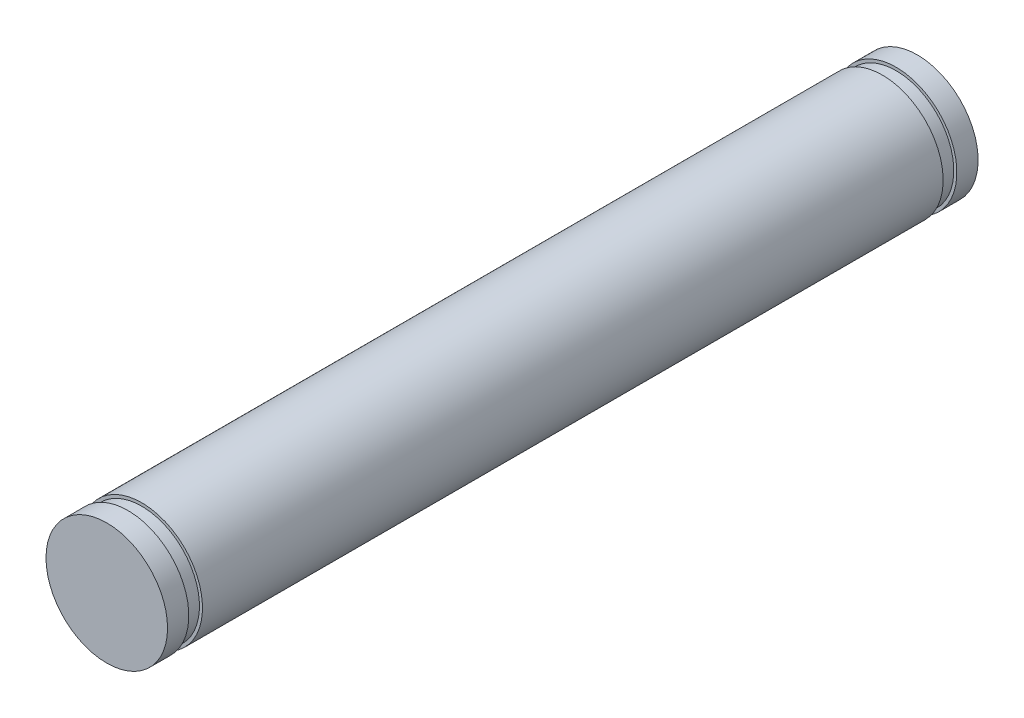
SolidWorks part; units mm, degrees
ref_plane "Front Plane" through (0, 0, 0) normal (0, 0, 1) x (1, 0, 0)
ref_plane "Top Plane" through (0, 0, 0) normal (0, 1, 0) x (1, 0, 0)
ref_plane "Right Plane" through (0, 0, 0) normal (1, 0, 0) x (0, 0, -1)
sketch "Sketch1" plane through (0, 0, 0) normal (0, 0, 1) x (1, 0, 0)
  line L0 (-4, 0) -> (4, 0) construction
  line L5 (0, 4) -> (0, -4) construction
  circle A1 centre (0, 0) radius 4
  point P7 (-4, 0)
  point P8 (4, 0)
  point P12 (0, -4)
  point P13 (0, 4)
  dimension "Diameter" = 8
sketch "Sketch2" plane through (0, 0, 0) normal (1, 0, 0) x (0, 0, -1)
  line L0 (-42, -4) -> (-42, 4) construction
  line L1 (50, -4) -> (-50, -4)
  line L2 (50, -4) -> (50, 4)
  line L3 (50, 4) -> (-50, 4)
  line L4 (-50, -4) -> (-50, 4)
  line L5 (50, -4) -> (-50, 4) construction
  line L6 (50, 4) -> (-50, -4) construction
  line L7 (42, -4) -> (42, 4) construction
  line L8 (-50, 3.44) -> (-49.44, 4) construction
  point P0 (0, 0)
  point P8 (-50, 4)
  point P9 (50, 4)
  point P14 (-42, 4)
  point P15 (-42, -4)
  point P16 (42, 4)
  point P17 (42, -4)
  point P25 (0, -4)
  dimension "Length" = 100
  dimension "D1" = 8
  dimension "D2" = 8
  dimension "Chamfer Typ," = 45
  dimension "D4" = 0.56
sketch "Sketch3" plane through (0, 0, 0) normal (0, 0, 1) x (1, 0, 0)
  circle A0 centre (0, 0) radius 4 construction
  circle A1 centre (0, 0) radius 4
extrude "Boss-Extrude1" add sketch "Sketch3" along normal up to vertex (50 mm away) and the other way up to vertex (50 mm away) up to point (0, 4, 50) other way up to point (0, 4, -50)
chamfer "Chamfer1" distance 0.56 angle 45 2 edges at (4, 0, -50) (4, 0, 50)
sketch "Sketch4" plane through (0, 0, 50) normal (0, 0, 1) x (1, 0, 0)
  circle A0 centre (0, 0) radius 14.5
  dimension "D1" = 29
extrude "Cut-Extrude1" cut sketch "Sketch4" against normal blind 22.01
sketch "Sketch5" plane through (0, 0, -50) normal (0, 0, -1) x (-1, 0, 0)
  circle A0 centre (0, 0) radius 6.5
  dimension "D1" = 13
extrude "Cut-Extrude2" cut sketch "Sketch5" against normal blind 24.638
sketch "Sketch6" plane through (0, 0, -25.362) normal (0, 0, -1) x (-1, 0, 0)
  circle A0 centre (0, 0) radius 4
  circle A1 centre (0, 0) radius 3.8
  circle A2 centre (0, 0) radius 4 construction
  dimension "D1" = 7.6
extrude "Cut-Extrude3" cut sketch "Sketch6" along normal blind 0.9 from offset 2.3 offset against normal yes
ref_plane "Plane1" through (0, 0, 1.314) normal (0, 0, -1) x (-1, 0, 0)
mirror "Mirror1" about plane through (0, 0, 1.314) normal (0, 0, -1) of "Cut-Extrude3"
equation "\"D1@Sketch2\"=\"Diameter@Sketch1\""
equation "\"D2@Sketch2\"=\"Diameter@Sketch1\""
equation "\"D1@Chamfer1\"=\"Diameter@Sketch1\"*.07"
equation "\"D4@Sketch2\"=\"Diameter@Sketch1\"*.07"
equation "\"D2@Chamfer1\"=\"Chamfer Typ,@Sketch2\""
